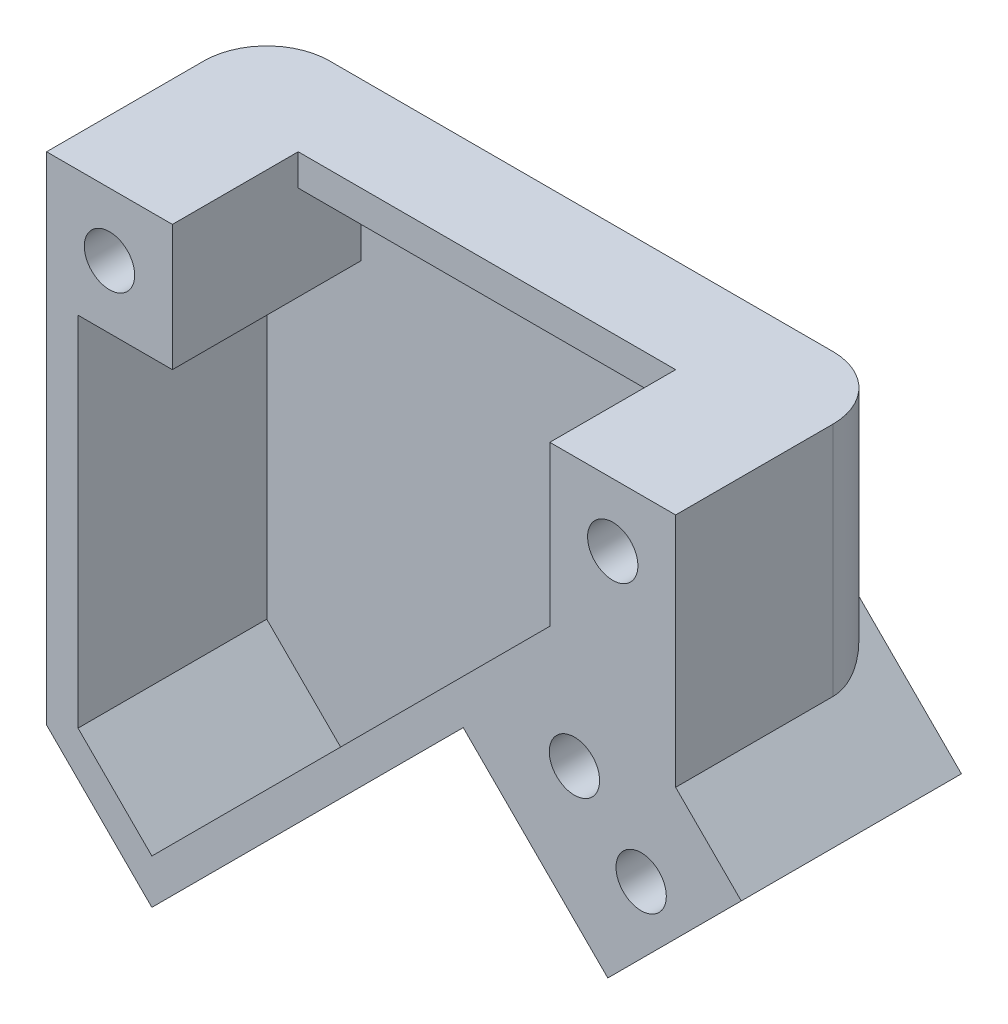
SolidWorks part; units mm, degrees
ref_plane "Front" through (0, 0, 0) normal (0, 0, 1) x (1, 0, 0)
ref_plane "Top" through (0, 0, 0) normal (0, 1, 0) x (1, 0, 0)
ref_plane "Right" through (0, 0, 0) normal (1, 0, 0) x (0, 0, -1)
sketch "Sketch1" plane through (0, 0, 0) normal (0, 0, 1) x (1, 0, 0)
  line L1 (0, 0) -> (20, 0)
  line L2 (20, -7.5) -> (17.8431, -5.3431) construction
  line L3 (17.8431, -13.8284) -> (29.1568, -25.1421) construction
  line L4 (29.1568, -25.1421) -> (33.3995, -20.8995) construction
  line L5 (33.3995, -20.8995) -> (22.0857, -9.5857) construction
  line L6 (13.2469, -9.2322) -> (3.3474, -19.1317)
  line L7 (3.3474, -19.1317) -> (0, -15.7843)
  line L8 (13.2469, -9.2322) -> (17.8431, -13.8284)
  line L9 (4, -1) -> (4, -4)
  line L10 (1, -4) -> (1, -15.3701)
  line L11 (17.8431, -13.8284) -> (22.0857, -9.5857)
  line L12 (22.0857, -9.5857) -> (20, -7.5)
  line L14 (4, -1) -> (16, -1)
  line L16 (1, -15.3701) -> (3.3474, -17.7175)
  line L17 (16, -1) -> (16, -5.0649)
  line L19 (4, -4) -> (1, -4)
  line L20 (16, -5.0649) -> (3.3474, -17.7175)
  line L21 (20, 0) -> (20, -7.5)
  line L22 (0, 0) -> (0, -15.7843)
extrude "Boss-Extrude1" add sketch "Sketch1" along normal blind 7
sketch "Sketch6" plane through (0, 0, 0) normal (0, 0, 1) x (1, 0, 0)
  line L0 (0, 0) -> (20, 0)
  line L1 (20, -7.5) -> (17.8431, -5.3431) construction
  line L2 (17.8431, -13.8284) -> (29.1568, -25.1421) construction
  line L3 (29.1568, -25.1421) -> (33.3995, -20.8995) construction
  line L4 (33.3995, -20.8995) -> (22.0857, -9.5857) construction
  line L5 (13.2469, -9.2322) -> (3.3474, -19.1317)
  line L6 (3.3474, -19.1317) -> (0, -15.7843)
  line L7 (13.2469, -9.2322) -> (17.8431, -13.8284)
  line L10 (17.8431, -13.8284) -> (22.0857, -9.5857)
  line L11 (22.0857, -9.5857) -> (20, -7.5)
  line L17 (20, 0) -> (20, -7.5)
  line L18 (0, 0) -> (0, -15.7843)
extrude "Boss-Extrude2" add sketch "Sketch6" along normal blind 1
sketch "Sketch5" plane through (0, 0, 0) normal (0, 0, 1) x (1, 0, 0)
  line L0 (10, 0) -> (10, -2) construction
  line L1 (10, -2) -> (18, -2) construction
  line L2 (20, 0) -> (0, 0) construction
  line L3 (18.9038, -10.6464) -> (19.9644, -11.7071) construction
  line L9 (18.9038, -10.6464) -> (16.7824, -8.5251) construction
  line L10 (2, -2) -> (10, -2) construction
  circle A4 centre (18.9038, -10.6464) radius 0.8
  circle A5 centre (16.7824, -8.5251) radius 0.8
  circle A6 centre (2, -2) radius 0.8
  circle A7 centre (18, -2) radius 0.8
extrude "Screw Holes" cut sketch "Sketch5" along normal through all
fillet "Fillet1" radius 2 3 edges at (20, -3.75, 0) (1.6737, -17.458, 0) (0, -7.8921, 0)
sketch "Sketch7" plane through (0, 0, 0) normal (0, 0, 1) x (1, 0, 0)
  line L0 (4, -4) -> (4, 0)
  line L2 (4, 0) -> (16, 0)
  line L3 (16, 0) -> (16, -4)
  line L5 (16, -4) -> (4, -4)
extrude "Cut-Extrude2" cut sketch "Sketch7" against normal blind 4 from offset 7
